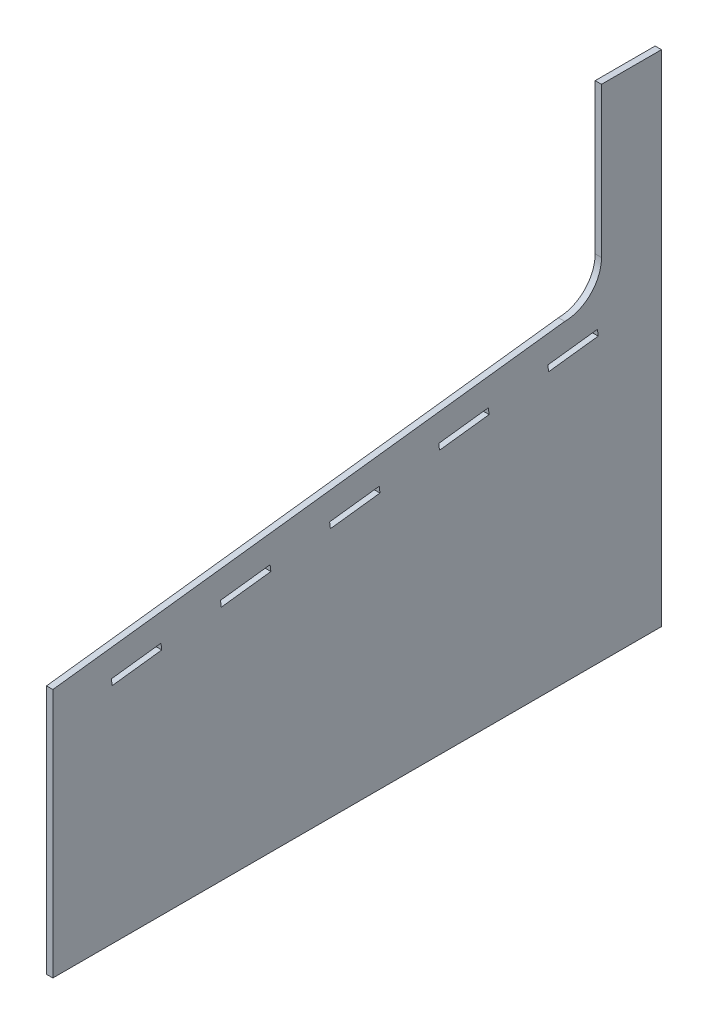
SolidWorks part; units mm, degrees
material "Beech"
ref_plane "Front Plane" through (0, 0, 0) normal (0, 0, 1) x (1, 0, 0)
ref_plane "Top Plane" through (0, 0, 0) normal (0, 1, 0) x (1, 0, 0)
ref_plane "Right Plane" through (0, 0, 0) normal (1, 0, 0) x (0, 0, -1)
sketch "Sketch1" plane through (0, 0, 0) normal (1, 0, 0) x (0, 0, -1)
  line L0 (0, 250) -> (512.2625, 312.8979)
  line L1 (0, 0) -> (609, 0)
  line L2 (0, 0) -> (0, 250)
  line L4 (609, 0) -> (609, 250)
  line L6 (609, 250) -> (609, 500)
  line L7 (609, 500) -> (549, 500)
  line L8 (549, 349.897) -> (549, 500)
  line L9 (0, 250) -> (609, 250) construction
  line L10 (512.2625, 312.8979) -> (609, 324.7758) construction
  arc A0 (512.2625, 312.8979) -> (549, 349.897) centre (512, 349.897) ccw
  point P10 (549, 349.897)
  dimension "D4" = 37
  dimension "D1" = 609
  dimension "D2" = 250
  dimension "D3" = 60
  dimension "D5" = 7
  dimension "D6" = 250
  dimension "D7" = 150.103
extrude "Boss-Extrude1" add sketch "Sketch1" along normal blind 6.35
sketch "Sketch2" plane through (6.35, 0, 0) normal (1, 0, 0) x (0, 0, -1)
  line L0 (512.2625, 312.8979) -> (609, 324.7758) construction
  line L1 (609, 0) -> (609, 500) construction
  line L2 (512.2625, 312.8979) -> (0, 250) construction
  line L3 (0, 222.7972) -> (609, 297.573) construction
  line L4 (0, 250) -> (0, 0) construction
  line L5 (58.5602, 229.9875) -> (59.3341, 223.6849)
  line L6 (59.3341, 223.6849) -> (108.9614, 229.7783)
  line L7 (108.9614, 229.7783) -> (108.1875, 236.081)
  line L8 (108.1875, 236.081) -> (58.5602, 229.9875)
  line L9 (217.3676, 249.4866) -> (167.7403, 243.3932)
  line L10 (167.7403, 243.3932) -> (168.5142, 237.0905)
  line L11 (168.5142, 237.0905) -> (218.1415, 243.184)
  line L12 (218.1415, 243.184) -> (217.3676, 249.4866)
  line L13 (326.5477, 262.8922) -> (276.9204, 256.7988)
  line L14 (276.9204, 256.7988) -> (277.6942, 250.4961)
  line L15 (277.6942, 250.4961) -> (327.3216, 256.5896)
  line L16 (327.3216, 256.5896) -> (326.5477, 262.8922)
  line L17 (435.7278, 276.2979) -> (386.1005, 270.2044)
  line L18 (386.1005, 270.2044) -> (386.8743, 263.9017)
  line L19 (386.8743, 263.9017) -> (436.5016, 269.9952)
  line L20 (436.5016, 269.9952) -> (435.7278, 276.2979)
  line L21 (544.9078, 289.7035) -> (495.2805, 283.61)
  line L22 (495.2805, 283.61) -> (496.0544, 277.3074)
  line L23 (496.0544, 277.3074) -> (545.6817, 283.4008)
  line L24 (545.6817, 283.4008) -> (544.9078, 289.7035)
  dimension "D1" = 27
  dimension "D2" = 50
  dimension "D3" = 6.35
  dimension "D4" = 59
extrude "Cut-Extrude1" cut sketch "Sketch2" against normal blind 6.35
